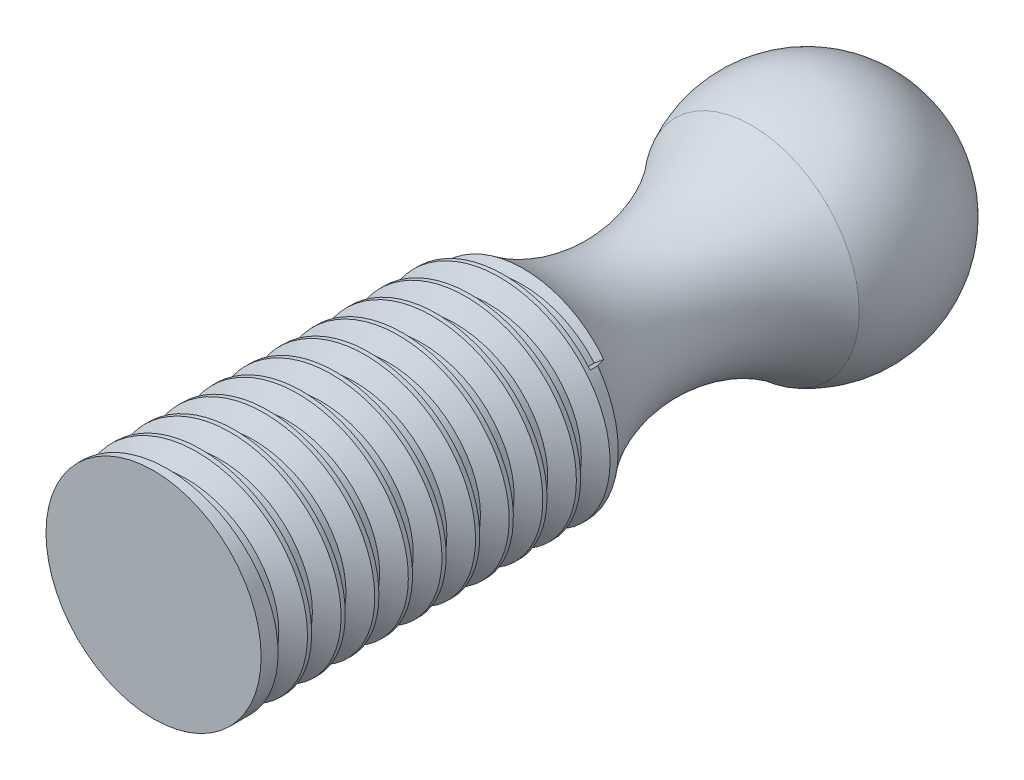
SolidWorks part; units mm, degrees
material "AISI 316L"
ref_plane "Piano frontale" through (0, 0, 0) normal (0, 0, 1) x (1, 0, 0)
ref_plane "Piano superiore" through (0, 0, 0) normal (0, 1, 0) x (1, 0, 0)
ref_plane "Piano destro" through (0, 0, 0) normal (1, 0, 0) x (0, 0, -1)
sketch "Schizzo2" plane through (0, 0, 0) normal (0, 0, 1) x (1, 0, 0)
  line L0 (13.398, -1.3546) -> (22.398, -1.3546)
  arc A0 (22.398, -1.3546) -> (13.398, -1.3546) centre (17.898, -1.3546) ccw
  dimension "D1" = 9
revolve "Rivoluzione1" add sketch "Schizzo2" angle 360 about L0
sketch "Schizzo3" plane through (0, 0, 0) normal (0, 0, 1) x (1, 0, 0)
  circle A0 centre (17.898, -1.3546) radius 4
  dimension "D1" = 8
extrude "Estrusione-Estrusione1" add sketch "Schizzo3" along normal blind 24.3
thread "Filettatura1" pitch 1.25 start angle 360, offset 0, length 13, pitch 1.25, diameter 8
ref_plane "Piano1" through (13.898, -1.3546, 24.3) normal (0, -1, 0) x (-1, 0, 0)
sketch "Profilo filettatura1" plane through (13.898, -1.3546, 24.3) normal (0, -1, 0) x (-1, 0, 0)
  line L0 (0, 0) -> (0, 1.25) construction
  line L11 (0, 0) -> (0, 1.0937)
  line L12 (0, 1.0937) -> (-0.6766, 0.7031)
  line L13 (-0.6766, 0.7031) -> (-0.6766, 0.3906)
  line L15 (-0.6766, 0.3906) -> (0, 0)
  line L17 (-0.6766, 0.5469) -> (0, 0.5469) construction
  point P2 (0, 0)
  dimension "Pitch" = 1.25
  dimension "Profile_Angle" = 60
  dimension "Profile_Land" = 0.3125
  dimension "Profile_Height" = 0.6766
sketch "Schizzo4" plane through (0, 0, 0) normal (0, 1, 0) x (1, 0, 0)
  line L0 (13.898, -2.0616) -> (21.898, -2.0616) construction
  line L1 (21.898, -11.3313) -> (21.898, -2.0616) construction
  line L2 (21.898, -2.0616) -> (21.898, -10.1117)
  line L3 (17.898, -2.0616) -> (17.898, -10.3938) construction
  arc A0 (21.898, -2.0616) -> (21.898, -10.1117) centre (26.3476, -6.0866) ccw
  spline S0 degree 2 poles (13.898, -23.2063) (13.898, -23.1281) (15.0696, -23.05) (16.2411, -22.9719) (17.898, -22.8937) (19.5549, -22.8156) (20.7264, -22.7375) (21.898, -22.6594) (21.898, -22.5812) (21.898, -22.5031) (20.7264, -22.425) (19.5549, -22.3469) (17.898, -22.2687) (16.2411, -22.1906) (15.0696, -22.1125) (13.898, -22.0344) (13.898, -21.9563) (13.898, -21.8781) (15.0696, -21.8) (16.2411, -21.7219) (17.898, -21.6437) (19.5549, -21.5656) (20.7264, -21.4875) (21.898, -21.4094) (21.898, -21.3312) (21.898, -21.2531) (20.7264, -21.175) (19.5549, -21.0969) (17.898, -21.0187) (16.2411, -20.9406) (15.0696, -20.8625) (13.898, -20.7844) (13.898, -20.7063) (13.898, -20.6281) (15.0696, -20.55) (16.2411, -20.4719) (17.898, -20.3937) (19.5549, -20.3156) (20.7264, -20.2375) (21.898, -20.1594) (21.898, -20.0812) (21.898, -20.0031) (20.7264, -19.925) (19.5549, -19.8469) (17.898, -19.7687) (16.2411, -19.6906) (15.0696, -19.6125) (13.898, -19.5344) (13.898, -19.4563) (13.898, -19.3781) (15.0696, -19.3) (16.2411, -19.2219) (17.898, -19.1437) (19.5549, -19.0656) (20.7264, -18.9875) (21.898, -18.9094) (21.898, -18.8312) (21.898, -18.7531) (20.7264, -18.675) (19.5549, -18.5969) (17.898, -18.5187) (16.2411, -18.4406) (15.0696, -18.3625) (13.898, -18.2844) (13.898, -18.2063) (13.898, -18.1281) (15.0696, -18.05) (16.2411, -17.9719) (17.898, -17.8937) (19.5549, -17.8156) (20.7264, -17.7375) (21.898, -17.6594) (21.898, -17.5812) (21.898, -17.5031) (20.7264, -17.425) (19.5549, -17.3469) (17.898, -17.2688) (16.2411, -17.1906) (15.0696, -17.1125) (13.898, -17.0344) (13.898, -16.9563) (13.898, -16.8781) (15.0696, -16.8) (16.2411, -16.7219) (17.898, -16.6438) (19.5549, -16.5656) (20.7264, -16.4875) (21.898, -16.4094) (21.898, -16.3312) (21.898, -16.2531) (20.7264, -16.175) (19.5549, -16.0969) (17.898, -16.0188) (16.2411, -15.9406) (15.0696, -15.8625) (13.898, -15.7844) (13.898, -15.7063) (13.898, -15.6281) (15.0696, -15.55) (16.2411, -15.4719) (17.898, -15.3938) (19.5549, -15.3156) (20.7264, -15.2375) (21.898, -15.1594) (21.898, -15.0812) (21.898, -15.0031) (20.7264, -14.925) (19.5549, -14.8469) (17.898, -14.7688) (16.2411, -14.6906) (15.0696, -14.6125) (13.898, -14.5344) (13.898, -14.4563) (13.898, -14.3781) (15.0696, -14.3) (16.2411, -14.2219) (17.898, -14.1438) (19.5548, -14.0656) (20.7264, -13.9875) (21.898, -13.9094) (21.898, -13.8312) (21.898, -13.7531) (20.7264, -13.675) (19.5548, -13.5969) (17.898, -13.5188) (16.2411, -13.4406) (15.0696, -13.3625) (13.898, -13.2844) (13.898, -13.2063) (13.898, -13.1281) (15.0696, -13.05) (16.2411, -12.9719) (17.898, -12.8938) (19.5548, -12.8156) (20.7264, -12.7375) (21.898, -12.6594) (21.898, -12.5812) (21.898, -12.5031) (20.7264, -12.425) (19.5548, -12.3469) (17.898, -12.2688) (16.2411, -12.1906) (15.0696, -12.1125) (13.898, -12.0344) (13.898, -11.9563) (13.898, -11.8781) (15.0696, -11.8) (16.2411, -11.7219) (17.898, -11.6438) (19.5548, -11.5656) (20.7264, -11.4875) (21.898, -11.4094) (21.898, -11.3312) (21.898, -11.2531) (20.7264, -11.175) (19.5548, -11.0969) (17.898, -11.0188) (16.2411, -10.9406) (15.0696, -10.8625) (13.898, -10.7844) (13.898, -10.7063) (13.898, -10.6281) (15.0696, -10.55) (16.2411, -10.4719) (17.898, -10.3938) (19.5548, -10.3156) (20.7264, -10.2375) (20.949, -10.2227) (21.1341, -10.207) knots 0 0 0 0.011364 0.011364 0.022727 0.022727 0.034091 0.034091 0.045455 0.045455 0.056818 0.056818 0.068182 0.068182 0.079545 0.079545 0.090909 0.090909 0.102273 0.102273 0.113636 0.113636 0.125 0.125 0.136364 0.136364 0.147727 0.147727 0.159091 0.159091 0.170455 0.170455 0.181818 0.181818 0.193182 0.193182 0.204545 0.204545 0.215909 0.215909 0.227273 0.227273 0.238636 0.238636 0.25 0.25 0.261364 0.261364 0.272727 0.272727 0.284091 0.284091 0.295455 0.295455 0.306818 0.306818 0.318182 0.318182 0.329545 0.329545 0.340909 0.340909 0.352273 0.352273 0.363636 0.363636 0.375 0.375 0.386364 0.386364 0.397727 0.397727 0.409091 0.409091 0.420455 0.420455 0.431818 0.431818 0.443182 0.443182 0.454545 0.454545 0.465909 0.465909 0.477273 0.477273 0.488636 0.488636 0.5 0.5 0.511364 0.511364 0.522727 0.522727 0.534091 0.534091 0.545455 0.545455 0.556818 0.556818 0.568182 0.568182 0.579545 0.579545 0.590909 0.590909 0.602273 0.602273 0.613636 0.613636 0.625 0.625 0.636364 0.636364 0.647727 0.647727 0.659091 0.659091 0.670455 0.670455 0.681818 0.681818 0.693182 0.693182 0.704545 0.704545 0.715909 0.715909 0.727273 0.727273 0.738636 0.738636 0.75 0.75 0.761364 0.761364 0.772727 0.772727 0.784091 0.784091 0.795455 0.795455 0.806818 0.806818 0.818182 0.818182 0.829545 0.829545 0.840909 0.840909 0.852273 0.852273 0.863636 0.863636 0.875 0.875 0.886364 0.886364 0.897727 0.897727 0.909091 0.909091 0.920455 0.920455 0.931818 0.931818 0.943182 0.943182 0.945483 0.945483 0.945483 weights 1 0.92388 1 0.92388 1 0.92388 1 0.92388 1 0.92388 1 0.92388 1 0.92388 1 0.92388 1 0.92388 1 0.92388 1 0.92388 1 0.92388 1 0.92388 1 0.92388 1 0.92388 1 0.92388 1 0.92388 1 0.92388 1 0.92388 1 0.92388 1 0.92388 1 0.92388 1 0.92388 1 0.92388 1 0.92388 1 0.92388 1 0.92388 1 0.92388 1 0.92388 1 0.92388 1 0.92388 1 0.92388 1 0.92388 1 0.92388 1 0.92388 1 0.92388 1 0.92388 1 0.92388 1 0.92388 1 0.92388 1 0.92388 1 0.92388 1 0.92388 1 0.92388 1 0.92388 1 0.92388 1 0.92388 1 0.92388 1 0.92388 1 0.92388 1 0.92388 1 0.92388 1 0.92388 1 0.92388 1 0.92388 1 0.92388 1 0.92388 1 0.92388 1 0.92388 1 0.92388 1 0.92388 1 0.92388 1 0.92388 1 0.92388 1 0.92388 1 0.92388 1 0.92388 1 0.92388 1 0.92388 1 0.92388 1 0.92388 1 0.92388 1 0.92388 1 0.92388 1 0.92388 1 0.92388 1 0.92388 1 0.92388 1 0.92388 1 0.92388 1 0.92388 1 0.92388 1 0.92388 1 0.984586 0.975414 construction
  dimension "D1" = 6
ref_axis "Assi1" through (17.898, -1.3546, 24.3) along (0, 0, -1)
ref_plane "Piano2" through (17.898, 0, 0) normal (1, 0, 0) x (0, 0, -1)
sketch "Schizzo5" plane through (17.898, 0, 0) normal (1, 0, 0) x (0, 0, -1)
  line L0 (-11.0188, -5.3546) -> (-2.0616, -5.3546) construction
  line L1 (-11.0188, -5.3546) -> (-2.0616, -5.3546)
  arc A0 (-11.0188, -5.3546) -> (-2.0616, -5.3546) centre (-6.5402, -10.7344) cw
  dimension "D1" = 7
revolve "Taglia-Rivoluzione2" cut sketch "Schizzo5" angle 360 about axis through (17.898, -1.3546, 24.3) along (0, 0, -1)
